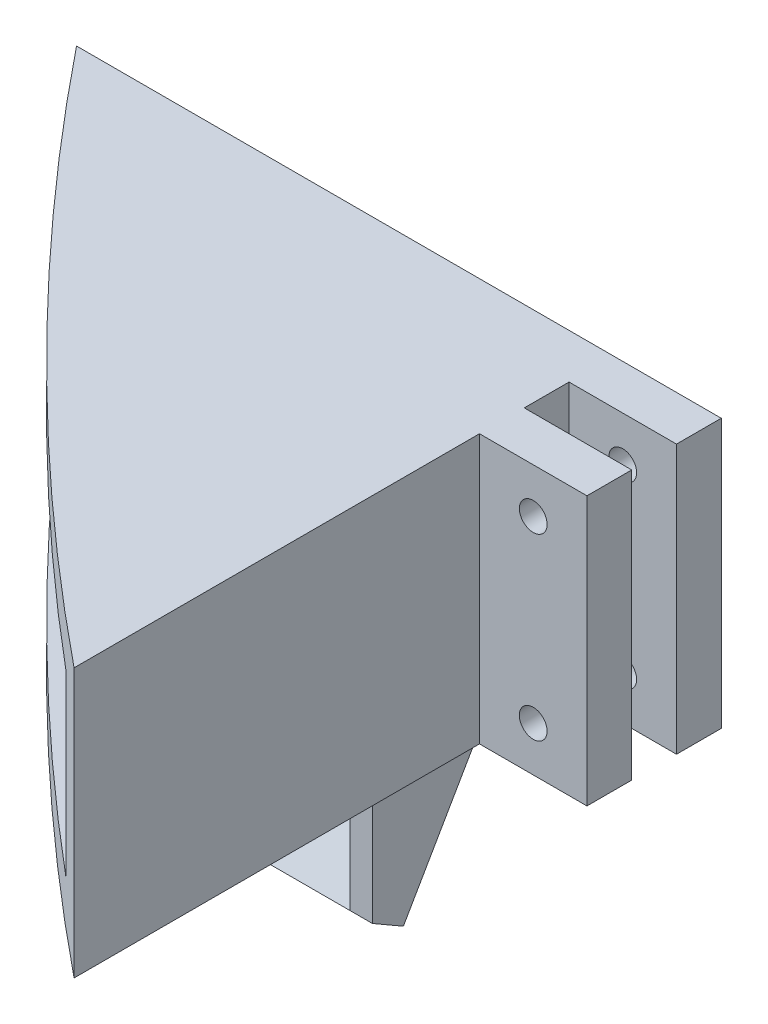
SolidWorks part; units mm, degrees
other "标注1"
sketch "草图28" plane through (2, -23.3827, 0) normal (0.0282, -0.8647, -0.5015) x (-0.6544, 0.3633, -0.6631)
ref_plane "前视基准面" through (0, 0, 0) normal (0, 0, 1) x (1, 0, 0)
ref_plane "上视基准面" through (0, 0, 0) normal (0, 1, 0) x (1, 0, 0)
ref_plane "右视基准面" through (0, 0, 0) normal (1, 0, 0) x (0, 0, -1)
sketch "草图1" plane through (0, 0, 0) normal (0, 1, 0) x (1, 0, 0)
  line L0 (0, 0) -> (-70, 0)
  line L2 (0, 0) -> (0, -5)
  line L3 (0, -5) -> (-10, -5)
  line L4 (-10, -5) -> (-10, -10)
  line L5 (-10, -10) -> (0, -10)
  line L6 (0, -10) -> (0, -15)
  line L7 (0, -15) -> (-10, -15)
  line L8 (-10, -15) -> (-10, -60.2761)
  arc A0 (-70, 0) -> (-10, -60.2761) centre (241.8847, 250.4554) ccw
  dimension "D3" = 400
  dimension "D1" = 70
  dimension "D2" = 61.1
  dimension "D4" = 5
  dimension "D5" = 5
  dimension "D6" = 5
  dimension "D7" = 10
extrude "凸台-拉伸1" add sketch "草图1" along normal blind 30
sketch "草图2" plane through (0, 0, 0) normal (0, 0, -1) x (-1, 0, 0)
  line L0 (0, 15) -> (23.3117, 15) construction
  line L1 (0, 30) -> (0, 0) construction
  line L2 (0, 30) -> (70, 30) construction
  circle A0 centre (4, 25) radius 1.55
  circle A1 centre (4, 5) radius 1.55
  dimension "D1" = 3.1
  dimension "D2" = 4
  dimension "D3" = 5
extrude "切除-拉伸1" cut sketch "草图2" against normal through all both and the other way through all
ref_plane "基准面11" through (0, 30, 0) normal (0, 1, 0) x (1, 0, 0)
sketch "草图6" plane through (0, 30, 0) normal (0, 1, 0) x (1, 0, 0)
  line L4 (-15, -15) -> (-15, -5)
  line L5 (-59.3918, -5) -> (-65.918, -5)
  line L6 (-15, -49.6033) -> (-15, -15)
  line L7 (0, -5) -> (-59.3918, -5)
  line L8 (-15, -49.6033) -> (-15, -15)
  line L9 (-15, -5) -> (-59.3918, -5)
  line L10 (-15, -49.6033) -> (-15, -56.1555)
  arc A2 (-70, 0) -> (-10, -60.2761) centre (241.8847, 250.4554) ccw construction
  arc A3 (-59.3918, -5) -> (-15, -49.6033) centre (241.8847, 250.4554) ccw
  arc A7 (-70, 0) -> (-10, -60.2761) centre (241.8847, 250.4554) ccw
  arc A8 (-65.918, -5) -> (-15, -56.1555) centre (241.8847, 250.4554) ccw
  dimension "D2" = 0
  dimension "D1" = 5
ref_plane "基准面15" through (0, 15, 0) normal (0, 1, 0) x (1, 0, 0)
sketch "草图9" plane through (0, 15, 0) normal (0, 1, 0) x (1, 0, 0)
  line L10 (-65.918, -5) -> (-59.3918, -5)
  line L11 (-15, -49.6033) -> (-15, -56.1555)
  line L12 (-15, -49.6033) -> (-15, -15)
  line L13 (0, -5) -> (-59.3918, -5)
  line L14 (-15, -49.6033) -> (-15, -15)
  line L15 (-15, -5) -> (-59.3918, -5)
  line L16 (-15, -15) -> (-15, -5)
  arc A2 (-59.3918, -5) -> (-15, -49.6033) centre (241.8847, 250.4554) ccw
  arc A5 (-65.918, -5) -> (-15, -56.1555) centre (241.8847, 250.4554) ccw
  arc A6 (-65.918, -5) -> (-15, -56.1555) centre (241.8847, 250.4554) ccw
  dimension "D2" = 0
  dimension "D1" = 5
extrude "切除-拉伸6" cut sketch "草图9" against normal mid plane 20
sketch "草图11" plane through (0, 15, 0) normal (0, 1, 0) x (1, 0, 0)
  line L0 (-15, -5) -> (-23, -5)
  line L1 (-15, -5) -> (-59.3918, -5) construction
  line L2 (-15, -5) -> (-15, -10)
  line L3 (-15, -15) -> (-15, -5) construction
  line L4 (-15, -10) -> (-23, -5)
  dimension "D1" = 8
  dimension "D2" = 5
extrude "凸台-拉伸3" add sketch "草图11" along normal mid plane 25
ref_plane "基准面16" through (0, 0, 0) normal (0, 0, -1) x (-1, 0, 0)
sketch "草图12" plane through (0, 0, 0) normal (1, 0, 0) x (0, 0, -1)
  line L1 (-15, 30) -> (-10, 30)
  line L2 (-15, 30) -> (-15, 0)
  line L3 (-15, 0) -> (-10, 0)
  line L4 (-10, 30) -> (-10, 0)
  line L5 (-5, 0) -> (0, 0)
  line L6 (-5, 0) -> (-5, 30)
  line L7 (-5, 30) -> (0, 30)
  line L8 (0, 0) -> (0, 30)
extrude "凸台-拉伸4" add sketch "草图12" along normal blind 2
sketch "草图17" plane through (0, 0, 0) normal (0, -1, 0) x (1, 0, 0)
  line L0 (2, 0) -> (-70, 0) construction
  line L1 (-45, 0) -> (-20, 0)
  line L2 (-45, 0) -> (-45, 25)
  line L3 (-45, 25) -> (-20, 25)
  line L4 (-20, 0) -> (-20, 25)
  dimension "D1" = 25
extrude "凸台-拉伸7" [suppressed] add sketch "草图17" along normal blind 40
sketch "草图18" [suppressed] plane through (-45, 0, 0) normal (-1, 0, 0) x (0, 0, 1)
  line L10 (0, 0) -> (25, -40)
  line L11 (25, -40) -> (0, -40)
  line L12 (25, -40) -> (0, -40) construction
  line L13 (0, -40) -> (0, 0)
extrude "切除-拉伸9" [suppressed] cut sketch "草图18" against normal blind 50
sketch "草图21" [suppressed] plane through (0, 0, 0) normal (0, -0.53, -0.848) x (-1, 0, 0)
  line L0 (20, -47.1699) -> (20, 0) construction
  line L1 (20, -47.1699) -> (45, -47.1699) construction
  circle A0 centre (32.5, -22.1699) radius 1.5
  circle A1 centre (32.5, -12.1699) radius 1.5
  circle A2 centre (32.5, -32.1699) radius 1.5
  dimension "D1" = 12.5
  dimension "D3" = 10
  dimension "D2" = 25
  dimension "D4" = 10
extrude "切除-拉伸12" [suppressed] cut sketch "草图21" against normal blind 7
sketch "草图22" [suppressed] plane through (-45, 0, 0) normal (-1, 0, 0) x (0, 0, 1)
  line L0 (7.217, -4) -> (21, -4)
  line L1 (21, -4) -> (21, -26.0528)
  line L2 (21, -26.0528) -> (7.217, -4)
  line L4 (25, 0) -> (0, 0) construction
  line L5 (25, -40) -> (0, 0) construction
  line L6 (0, 0) -> (60.2761, 0) construction
  line L7 (25, -40) -> (25, 0) construction
  dimension "D1" = 4
  dimension "D2" = 4
  dimension "D3" = 4
extrude "切除-拉伸13" [suppressed] cut sketch "草图22" against normal blind 500
sketch "草图23" [suppressed] plane through (0, 0, 25) normal (0, 0, 1) x (1, 0, 0)
  line L0 (-20, 0) -> (-45, 0) construction
  line L1 (-41, -4) -> (-24, -4)
  line L2 (-41, -4) -> (-41, -25)
  line L3 (-41, -25) -> (-24, -25)
  line L4 (-24, -4) -> (-24, -25)
  line L5 (-45, -40) -> (-45, 0) construction
  line L6 (-20, -40) -> (-20, 0) construction
  line L7 (-20, -40) -> (-45, -40) construction
  dimension "D1" = 4
  dimension "D2" = 4
  dimension "D3" = 4
  dimension "D4" = 15
extrude "切除-拉伸14" [suppressed] cut sketch "草图23" against normal blind 4
ref_plane "基准面17" through (0, 0, 0) normal (0, -0.5, -0.866) x (-1, 0, 0)
sketch "草图24" plane through (0, 0, 0) normal (0, -0.5, -0.866) x (-1, 0, 0)
  line L0 (-2, 0) -> (70, 0) construction
  line L1 (20, 0) -> (42, 0)
  line L2 (10, -5) -> (10, -2.5) construction
  line L3 (20, 0) -> (42, 0)
  line L4 (20, 0) -> (20, -27)
  line L5 (20, -27) -> (42, -27)
  line L6 (42, 0) -> (42, -27)
  line L7 (28, 0) -> (28, -27) construction
  line L8 (28, -15) -> (38, -15) construction
  line L9 (28, -15) -> (36.6603, -10) construction
  line L10 (28, -15) -> (33, -6.3397) construction
  line L11 (28, -15) -> (36.6603, -20) construction
  line L12 (28, -15) -> (33, -23.6603) construction
  circle A0 centre (28, -15) radius 1.55
  circle A1 centre (28, -15) radius 10 construction
  circle A2 centre (33, -6.3397) radius 1.55
  circle A3 centre (36.6603, -10) radius 1.55
  circle A4 centre (38, -15) radius 1.55
  circle A5 centre (36.6603, -20) radius 1.55
  circle A6 centre (33, -23.6603) radius 1.55
  dimension "D5" = 3.1
  dimension "D6" = 20
  dimension "D1" = 22
  dimension "D2" = 27
  dimension "D3" = 10
  dimension "D4" = 8
  dimension "D7" = 30
  dimension "D8" = 12
extrude "凸台-拉伸8" add sketch "草图24" against normal blind 4 contours L6 L1 L4 L5 A6 A5 A4 A3 A2 A0 region at (-30.7342, -11.5841, 6.6881)
sketch "草图25" plane through (-20, 0, 0) normal (1, 0, 0) x (0, 0, -1)
  line L0 (-16.9641, -21.3827) -> (-16.9641, 0)
  line L1 (-60.2761, 0) -> (-15, 0) construction
  line L2 (-16.9641, 0) -> (-4.6188, 0)
  line L3 (-16.9641, -21.3827) -> (-4.6188, 0)
extrude "凸台-拉伸9" add sketch "草图25" against normal blind 2.5
sketch "草图27" plane through (-42, 0, 0) normal (-1, 0, 0) x (0, 0, 1)
  line L0 (0, 0) -> (16.9641, 0)
  line L1 (16.9641, 0) -> (16.9641, -21.3827)
  line L2 (16.9641, -21.3827) -> (13.5, -23.3827)
  line L3 (13.5, -23.3827) -> (0, 0)
extrude "凸台-拉伸10" add sketch "草图27" along normal blind 2.5
